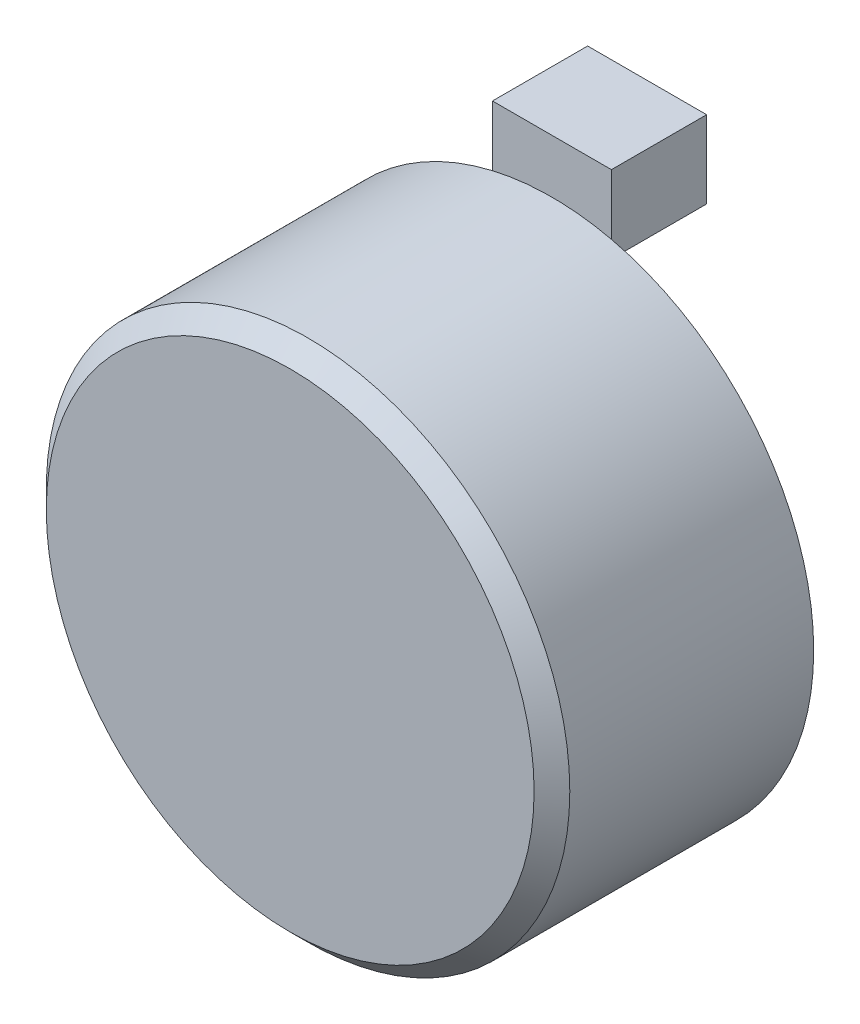
SolidWorks part; units mm, degrees
ref_plane "Front Plane" through (0, 0, 0) normal (0, 0, 1) x (1, 0, 0)
ref_plane "Top Plane" through (0, 0, 0) normal (0, 1, 0) x (1, 0, 0)
ref_plane "Right Plane" through (0, 0, 0) normal (1, 0, 0) x (0, 0, -1)
sketch "SK_Body" plane through (0, 0, 0) normal (0, 1, 0) x (1, 0, 0)
  line L0 (0, -10) -> (0, 54) construction
  line L1 (0, 0) -> (41, 0)
  line L2 (41, 0) -> (44, 3)
  line L3 (44, 3) -> (44, 44)
  line L4 (44, 44) -> (41, 44)
  line L5 (41, 44) -> (0, 44)
  line L6 (0, 44) -> (0, 0)
  dimension "P1" = 10
  dimension "P2" = 54
  dimension "R_front" = 41
  dimension "P4" = 44
  dimension "P5" = 3
  dimension "R_body" = 44
  dimension "L_body" = 44
  dimension "P8" = 41
  dimension "P9" = 44
  dimension "P10" = 44
revolve "Housing_Body" add sketch "SK_Body" angle 360 about L0
ref_plane "PL_Rear" through (0, 0, -44) normal (0, 0, 1) x (1, 0, 0)
sketch "SK_RearHole" plane through (0, 0, -44) normal (0, 0, 1) x (1, 0, 0)
  circle A0 centre (37, 0) radius 1.25
  dimension "D_rh" = 2.5
  dimension "R_rh" = 37
extrude "Rear_Tapped_Hole" cut sketch "SK_RearHole" along normal blind 8
ref_axis "AX_Joint" through (0, 0, -63) along (0, 0, 1)
pattern_circular "Rear_Hole_Pattern" count 6 over 360 about axis through (0, 0, -63) along (0, 0, 1) of "Rear_Tapped_Hole"
sketch "SK_Connector" plane through (0, 0, -44) normal (0, 0, 1) x (1, 0, 0)
  line L0 (-10, 40) -> (10, 40)
  line L1 (10, 40) -> (10, 53)
  line L2 (10, 53) -> (-10, 53)
  line L3 (-10, 53) -> (-10, 40)
  dimension "P1" = 10
  dimension "P2" = 40
  dimension "P3" = 10
  dimension "P4" = 40
  dimension "P5" = 10
  dimension "P6" = 53
  dimension "P7" = 10
  dimension "P8" = 53
extrude "Connector_Zone" add sketch "SK_Connector" against normal blind 16
equation "\"D_act\" = 88"
equation "\"L_housing\" = 44"
equation "\"PCD_rear\" = 74"
equation "\"D_rear_hole\" = 2.5"
equation "\"D_bearing_boss\" = 52"
equation "\"R_front@SK_Body\" = \"D_act\"/2-3.0"
equation "\"R_body@SK_Body\" = \"D_act\"/2"
equation "\"L_body@SK_Body\" = \"L_housing\""
equation "\"D_rh@SK_RearHole\" = \"D_rear_hole\""
equation "\"R_rh@SK_RearHole\" = \"PCD_rear\"/2"
